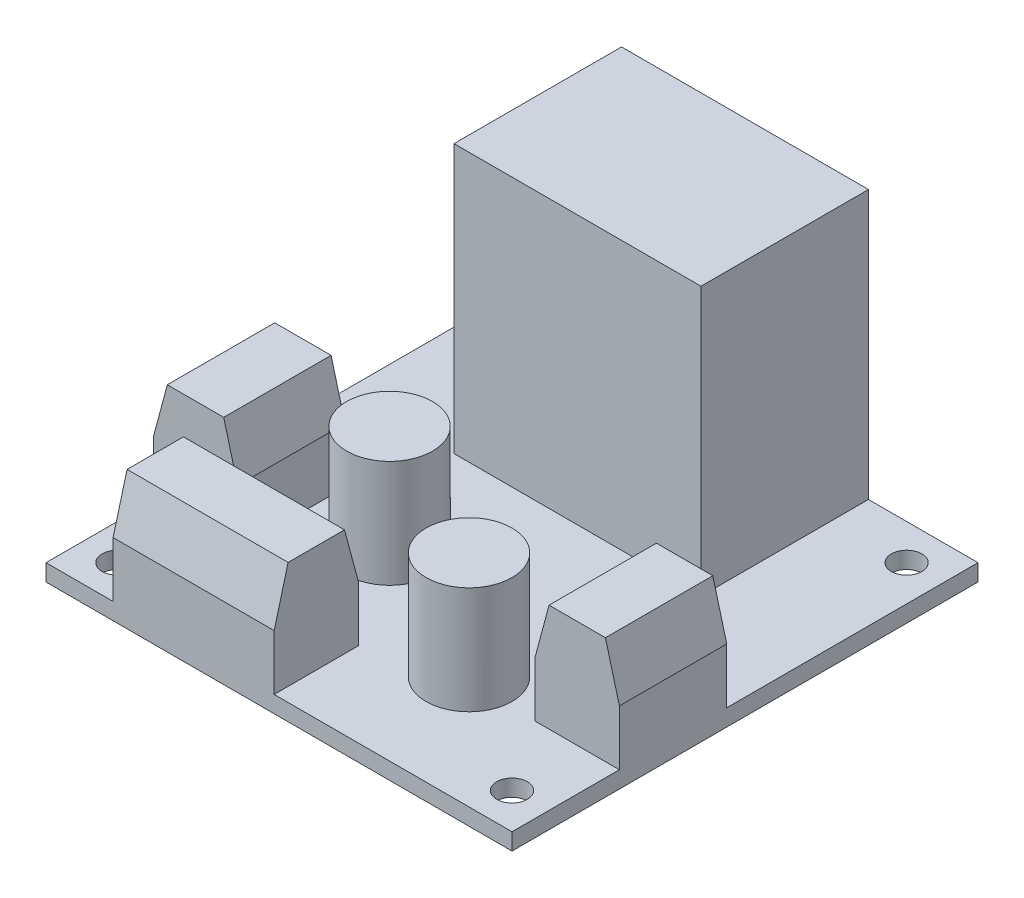
SolidWorks part; units mm, degrees
note: The reader was unsure of these and kept them because the rebuilt part matched: shared geometry of "Sketch3<3>", "Sketch3<4>".
ref_plane "Front Plane" through (0, 0, 0) normal (0, 0, 1) x (1, 0, 0)
ref_plane "Top Plane" through (0, 0, 0) normal (0, 1, 0) x (1, 0, 0)
ref_plane "Right Plane" through (0, 0, 0) normal (1, 0, 0) x (0, 0, -1)
sketch "Sketch2" plane through (0, 0, 0) normal (0, 1, 0) x (1, 0, 0)
  line L1 (0, 0) -> (43.4, 0)
  line L2 (0, 0) -> (0, 43.4)
  line L3 (0, 43.4) -> (43.4, 43.4)
  line L4 (43.4, 0) -> (43.4, 43.4)
  dimension "D1" = 43.4
  dimension "D2" = 43.4
extrude "Boss-Extrude1" add sketch "Sketch2" along normal blind 1.56
sketch "Sketch3" plane through (0, 1.56, 0) normal (0, 1, 0) x (1, 0, 0)
  line L0 (21.7, 43.4) -> (21.7, 0) construction
  line L1 (43.4, 43.4) -> (0, 43.4) construction
  line L2 (0, 0) -> (43.4, 0) construction
  line L3 (0, 43.4) -> (0, 0) construction
  line L4 (10.2, 43.4) -> (33.2, 43.4)
  line L5 (10.2, 43.4) -> (10.2, 27.8)
  line L6 (10.2, 27.8) -> (33.2, 27.8)
  line L7 (33.2, 43.4) -> (33.2, 27.8)
  line L8 (0, 10) -> (7.85, 10)
  line L9 (0, 10) -> (0, 20)
  line L10 (0, 20) -> (7.85, 20)
  line L11 (7.85, 10) -> (7.85, 20)
  line L12 (43.4, 0) -> (43.4, 43.4) construction
  line L13 (6.25, 0) -> (21.25, 0)
  line L14 (6.25, 0) -> (6.25, 7.85)
  line L15 (6.25, 7.85) -> (21.25, 7.85)
  line L16 (21.25, 0) -> (21.25, 7.85)
  line L17 (43.4, 20) -> (35.55, 20)
  line L18 (35.55, 10) -> (35.55, 20)
  line L19 (43.4, 10) -> (35.55, 10)
  line L20 (43.4, 10) -> (43.4, 20)
  line L21 (0, 21.7) -> (43.4, 21.7) construction
  circle A0 centre (15, 17) radius 4
  circle A1 centre (28.9, 10.5) radius 4
  circle A2 centre (3.325, 40.075) radius 1.425
  circle A6 centre (40.075, 40.075) radius 1.425
  circle A7 centre (40.075, 3.325) radius 1.425
  circle A8 centre (3.325, 3.325) radius 1.425
  point P10 (21.7, 43.4)
  line M19 (0, 43.4) -> (0, 0)
  line M20 (0, 0) -> (43.4, 0)
  line M21 (43.4, 0) -> (43.4, 43.4)
  dimension "D6" = 8
  dimension "D14" = 2.85
  dimension "D12" = 36.75
  dimension "D1" = 15.6
  dimension "D2" = 23
  dimension "D3" = 10
  dimension "D4" = 7.85
  dimension "D5" = 15
  dimension "D7" = 15
  dimension "D8" = 17
  dimension "D9" = 10.5
  dimension "D10" = 14.5
  dimension "D11" = 36.75
  dimension "D15" = 6.25
  dimension "D16" = 10
extrude "Boss-Extrude2" add sketch "Sketch3" along normal blind 25 contours L5 L4 L7 L6
extrude "Boss-Extrude3" add sketch "Sketch3<3>" along normal blind 10 contours A0 | L8 L11 L10 M19 | L16 L15 L14 M20 | A1 | L19 L17 L18 M21 | L6 L7 L4 L5
sketch "Sketch3<3>" plane through (0, 1.56, 0) normal (0, 1, 0) x (1, 0, 0) same geometry as "Sketch3"
chamfer "Chamfer1" distance 1.3 angle 75 6 edges at (13.75, 11.56, 0) (13.75, 11.56, -7.85) (43.4, 11.56, -15) (35.55, 11.56, -15) (7.85, 11.56, -15) (0, 11.56, -15)
extrude "Cut-Extrude1" cut sketch "Sketch3<4>" against normal through all
sketch "Sketch3<4>" plane through (0, 1.56, 0) normal (0, 1, 0) x (1, 0, 0) same geometry as "Sketch3"
